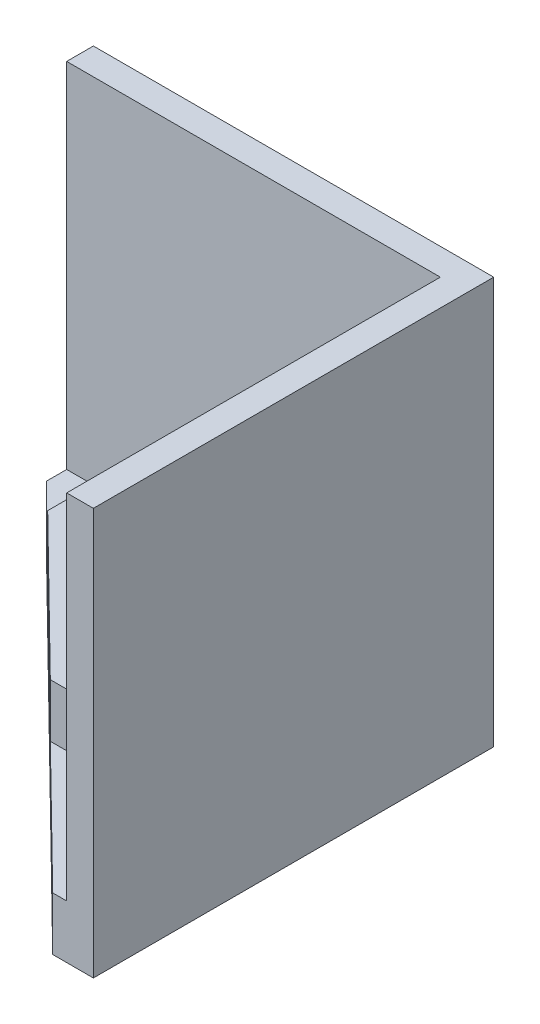
SolidWorks part; units mm, degrees
ref_plane "Front" through (0, 0, 0) normal (0, 0, 1) x (1, 0, 0)
ref_plane "Top" through (0, 0, 0) normal (0, 1, 0) x (1, 0, 0)
ref_plane "Right" through (0, 0, 0) normal (1, 0, 0) x (0, 0, -1)
sketch "Sketch1" plane through (0, 0, 0) normal (0, 1, 0) x (1, 0, 0)
  line L0 (-49.4663, 5.5479) -> (17.9137, -60.6289)
  line L1 (-49.4663, 14.3711) -> (25.5337, 14.3711)
  line L2 (-49.4663, 14.3711) -> (-49.4663, -60.6289)
  line L3 (-49.4663, -60.6289) -> (25.5337, -60.6289)
  line L4 (25.5337, 14.3711) -> (25.5337, -60.6289)
  point P6 (17.9137, -26.2689)
  point P7 (-25.2663, 5.5479)
  dimension "D1" = 75
  dimension "D2" = 75
extrude "Boss-Extrude1" add sketch "Sketch1" along normal blind 10 contours L4 L1 L2 L0 L3 region at (-2.091, 0, 12.9903)
sketch "Sketch3" plane through (0, 10, 0) normal (0, 1, 0) x (1, 0, 0)
  line L0 (-49.4663, 9.3711) -> (20.5337, 9.3711)
  line L1 (20.5337, 9.3711) -> (20.5337, -60.6289)
  line L5 (25.5337, -60.6289) -> (25.5337, 14.3711)
  line L6 (25.5337, 14.3711) -> (-49.4663, 14.3711)
  line L7 (-49.4663, 14.3711) -> (-49.4663, 5.5479)
  line L8 (-49.4663, 5.5479) -> (17.9137, -60.6289)
  line L9 (17.9137, -60.6289) -> (25.5337, -60.6289)
  line L10 (25.5337, -60.6289) -> (25.5337, 14.3711)
  line L11 (25.5337, 14.3711) -> (-49.4663, 14.3711)
  line L12 (-49.4663, 14.3711) -> (-49.4663, 5.5479)
  line L13 (-49.4663, 5.5479) -> (17.9137, -60.6289)
  line L14 (17.9137, -60.6289) -> (25.5337, -60.6289)
  line M8 (25.5337, -60.6289) -> (25.5337, 14.3711)
  line M9 (25.5337, 14.3711) -> (-49.4663, 14.3711)
  line M10 (-49.4663, 14.3711) -> (-49.4663, 5.5479)
  line M12 (17.9137, -60.6289) -> (25.5337, -60.6289)
  dimension "D2" = 5
  dimension "D3" = 5
  dimension "D1" = 0
extrude "Boss-Extrude3" add sketch "Sketch3" along normal blind 76.2 from surface contours L0 L1 M12 M8 M9 M10 region at (-48.4057, 10, -11.8711) starting at face at (-5.9903, 0, 17.3936)
sketch "Sketch2" plane through (0, 10, 0) normal (0, 1, 0) x (1, 0, 0)
  line L1 (-7.9143, 9.3711) -> (20.5337, 9.3711)
  line L2 (-7.9143, 9.3711) -> (-7.9143, -19.0769)
  line L3 (-7.9143, -19.0769) -> (20.5337, -19.0769)
  line L4 (20.5337, 9.3711) -> (20.5337, -19.0769)
  line L5 (47.1863, 26.5577) -> (-34.5669, 26.5577)
  line L6 (47.1863, 26.5577) -> (47.1863, -36.2636)
  line L7 (47.1863, -36.2636) -> (-34.5669, -36.2636)
  line L8 (-34.5669, 26.5577) -> (-34.5669, -36.2636)
  line L9 (20.5337, 9.3711) -> (-49.4663, 9.3711)
  line L10 (20.5337, 9.3711) -> (-49.4663, 9.3711)
  line L11 (-49.4663, 9.3711) -> (-49.4663, 5.5479)
  line L12 (-49.4663, 5.5479) -> (17.9137, -60.6289)
  line L13 (17.9137, -60.6289) -> (20.5337, -60.6289)
  line L16 (-49.4663, 9.3711) -> (-49.4663, 5.5479)
  line L17 (-49.4663, 5.5479) -> (17.9137, -60.6289)
  line L18 (17.9137, -60.6289) -> (20.5337, -60.6289)
  line L20 (-7.9143, 12.8595) -> (-34.5669, 12.8595)
  line L21 (-7.9143, 12.8595) -> (-7.9143, 1.7589)
  line L22 (-7.9143, 1.7589) -> (-34.5669, 1.7589)
  line L23 (-34.5669, 12.8595) -> (-34.5669, 1.7589)
  line L28 (20.5337, -60.6289) -> (20.5337, 9.3711)
  line L29 (20.5337, -60.6289) -> (20.5337, 9.3711)
  point P12 (-7.9143, -4.8529)
  point P13 (-34.5669, -4.8529)
  point P14 (6.3097, -19.0769)
  point P15 (6.3097, -36.2636)
  dimension "D4" = 28.448
  dimension "D5" = 28.448
  dimension "D1" = 0
extrude "Boss-Extrude2" add sketch "Sketch2" along normal blind 10 contours L2 L22 L8 L7 L20 L1 L4 L3 region at (-8.5838, 10, 8.659)
